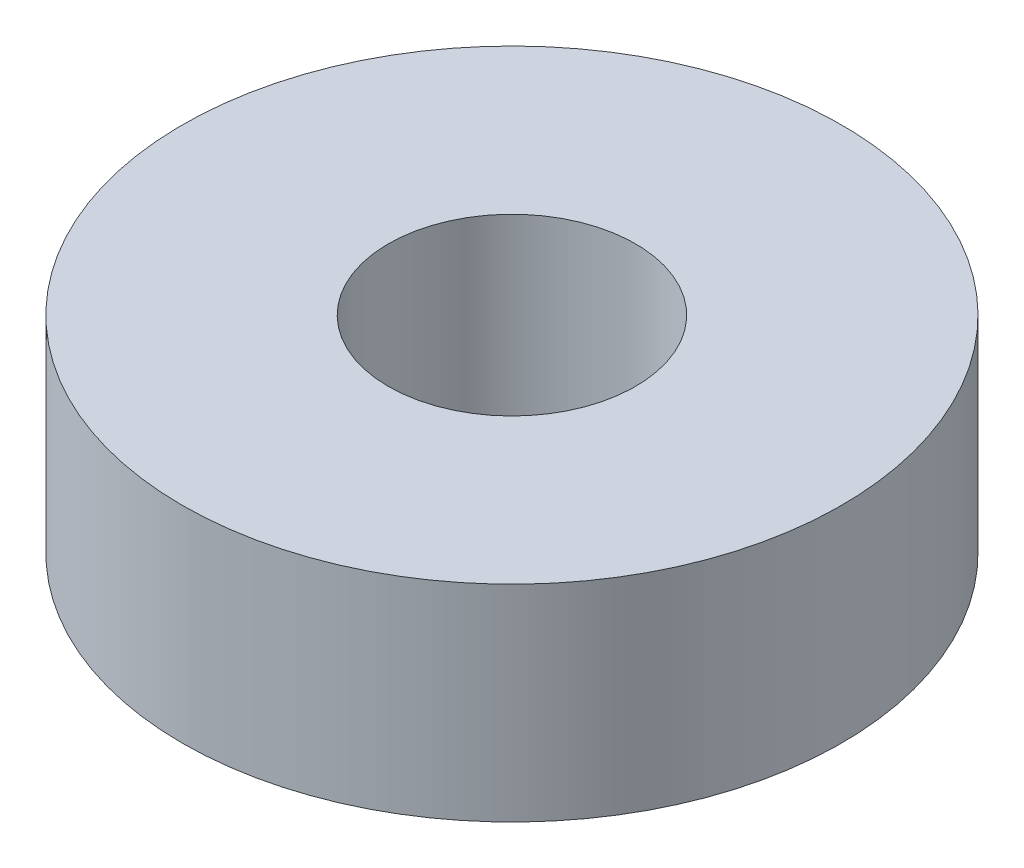
SolidWorks part; units mm, degrees
ref_plane "Front Plane" through (0, 0, 0) normal (0, 0, 1) x (1, 0, 0)
ref_plane "Top Plane" through (0, 0, 0) normal (0, 1, 0) x (1, 0, 0)
ref_plane "Right Plane" through (0, 0, 0) normal (1, 0, 0) x (0, 0, -1)
sketch "Sketch1" plane through (0, 0, 0) normal (0, 1, 0) x (1, 0, 0)
  circle A0 centre (0, 0) radius 40
  dimension "FLANGE_OD" = 80
extrude "Boss-Extrude1" add sketch "Sketch1" along normal blind 25
sketch "Sketch2" plane through (0, 0, 0) normal (0, 1, 0) x (1, 0, 0)
  circle A0 centre (0, 0) radius 15
  dimension "BORE_D" = 30
extrude "Cut-Extrude1" cut sketch "Sketch2" along normal through all
sketch "Sketch3" plane through (0, 25, 0) normal (0, 1, 0) x (1, 0, 0)
  circle A0 centre (0, 0) radius 9.9525 construction
  circle A1 centre (-9.9525, 0) radius 2.9477
  dimension "BOLT_D" = 5.8953
  dimension "BOLT_PCD" = 19.9049
extrude "Cut-Extrude2" cut sketch "Sketch3" against normal blind 18.2983 rebuild error yes
pattern_circular "CirPattern1" count 4 over 360 rebuild error yes
